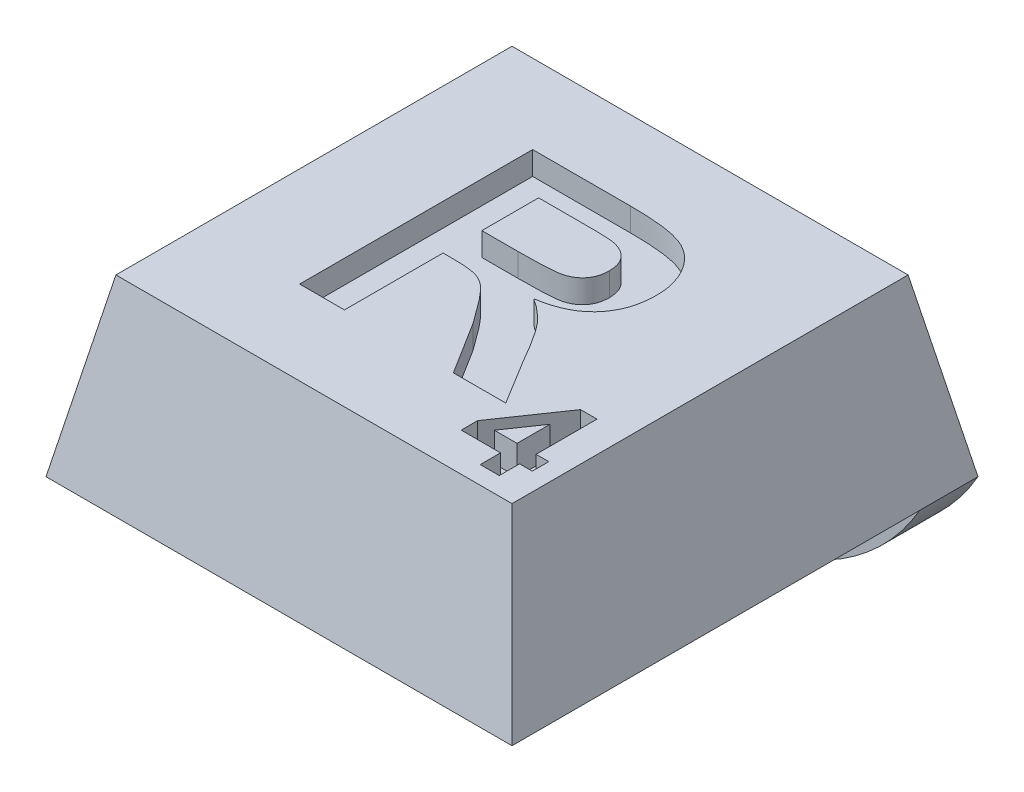
SolidWorks part; units mm, degrees
ref_plane "Front Plane" through (0, 0, 0) normal (0, 0, 1) x (1, 0, 0)
ref_plane "Top Plane" through (0, 0, 0) normal (0, 1, 0) x (1, 0, 0)
ref_plane "Right Plane" through (0, 0, 0) normal (1, 0, 0) x (0, 0, -1)
sketch "Sketch1" plane through (0, 0, 0) normal (0, 1, 0) x (1, 0, 0)
  line L1 (0, 0) -> (8, 0)
  line L2 (0, 0) -> (0, 8)
  line L3 (0, 8) -> (8, 8)
  line L4 (8, 0) -> (8, 8)
  dimension "D1" = 8
  dimension "D2" = 8
extrude "Boss-Extrude1" add sketch "Sketch1" along normal blind 3
sketch "Sketch2" plane through (0, 0, 0) normal (0, 0, 1) x (1, 0, 0)
  line L0 (0, 0) -> (0.6, 3)
  line L1 (0, 3) -> (8, 3) construction
  line L2 (0.6, 3) -> (0, 3)
  line L3 (0, 3) -> (0, 0)
  line L4 (8, 0) -> (7.4, 3)
  line L5 (7.4, 3) -> (8, 3)
  line L6 (8, 3) -> (8, 0)
  dimension "D1" = 0.6
  dimension "D2" = 0.6
extrude "Cut-Extrude1" cut sketch "Sketch2" against normal through all both and the other way through all
sketch "Sketch3" plane through (0, 0, 0) normal (1, 0, 0) x (0, 0, -1)
  line L0 (0, 0) -> (0.6, 3)
  line L1 (8, 3) -> (0, 3) construction
  line L2 (0.6, 3) -> (0, 3)
  line L3 (0, 3) -> (0, 0)
  line L4 (8, 3) -> (7.4, 3)
  line L5 (7.4, 3) -> (8, 0)
  line L6 (8, 3) -> (8, 0)
  dimension "D1" = 0.6
  dimension "D2" = 0.6
extrude "Cut-Extrude2" cut sketch "Sketch3" along normal blind 11
sketch "Sketch4" plane through (0, 0, 0) normal (0, -1, 0) x (1, 0, 0)
  line L0 (8, 0) -> (8, -8) construction
  line L3 (0, 0) -> (8, 0) construction
  circle A0 centre (4, -3.75) radius 1.75
  dimension "D1" = 3.5
  dimension "D2" = 4
  dimension "D3" = 3.75
extrude "Cut-Extrude3" cut sketch "Sketch4" against normal blind 0.4
sketch "Sketch5" plane through (0, 0, 0) normal (0, -1, 0) x (1, 0, 0)
  line L0 (8, 0) -> (8, -8) construction
  line L1 (0, -8) -> (8, -8)
  line L2 (0, -8) -> (0, -7)
  line L3 (0, -7) -> (8, -7)
  line L4 (8, -8) -> (8, -7)
  dimension "D1" = 1
extrude "Boss-Extrude2" add sketch "Sketch5" along normal blind 2
fillet "Fillet1" radius 4 2 edges at (8, -2, -7.5) (0, -2, -7.5)
sketch "Sketch6" plane through (0, 3, 0) normal (0, 1, 0) x (1, 0, 0)
  text T0 "R" font "Arial" height 4
extrude "Cut-Extrude4" cut sketch "Sketch6" against normal blind 0.4
sketch "Sketch7" plane through (0, 3, 0) normal (0, 1, 0) x (1, 0, 0)
  text T0 "4" font "Arial" height 1.7
extrude "Cut-Extrude5" cut sketch "Sketch7" against normal blind 0.5
